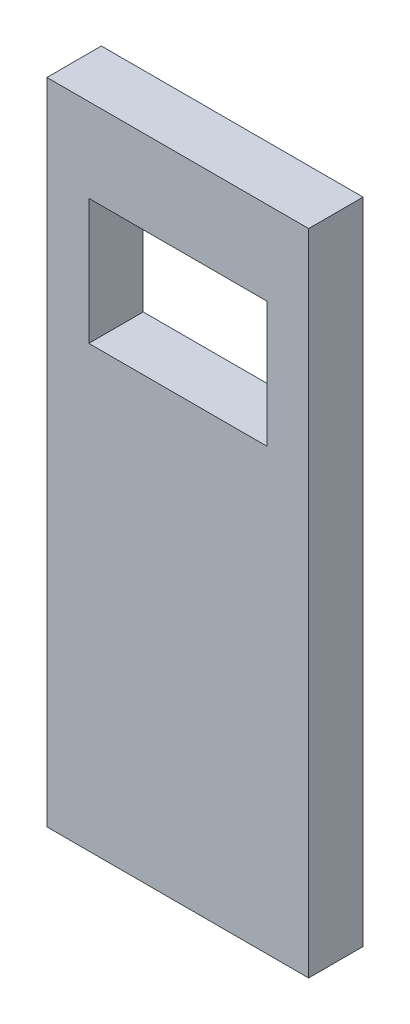
SolidWorks part; units mm, degrees
ref_plane "Front Plane" through (0, 0, 0) normal (0, 0, 1) x (1, 0, 0)
ref_plane "Top Plane" through (0, 0, 0) normal (0, 1, 0) x (1, 0, 0)
ref_plane "Right Plane" through (0, 0, 0) normal (1, 0, 0) x (0, 0, -1)
sketch "Sketch1" plane through (0, 0, 0) normal (0, 0, 1) x (1, 0, 0)
  line L0 (0, 62) -> (0, 42)
  line L1 (0, 62) -> (25, 62)
  line L2 (0, 42) -> (0, 37)
  line L3 (25, 0) -> (0, 0)
  line L4 (4, 54) -> (21, 54)
  line L5 (4, 42) -> (21, 42)
  line L6 (4, 54) -> (4, 42)
  line L7 (21, 54) -> (21, 42)
  line L8 (0, 42) -> (25, 42) construction
  line L9 (0, 37) -> (25, 37) construction
  line L10 (0, 37) -> (0, 25)
  line L11 (0, 25) -> (0, 20)
  line L12 (25, 42) -> (25, 37)
  line L13 (25, 62) -> (25, 42)
  line L14 (0, 20) -> (0, 0)
  line L15 (25, 37) -> (25, 25)
  line L16 (25, 25) -> (25, 20)
  line L17 (25, 20) -> (25, 0)
  line L18 (0, 25) -> (25, 25) construction
  line L19 (25, 20) -> (0, 20) construction
  line L20 (12.5, -0.0005) -> (12.5, 4.0956) construction
  point P18 (12.5, 42)
  point P20 (12.5, 54)
  point P21 (12.5, 62)
  dimension "D1" = 20
  dimension "D2" = 12
  dimension "D3" = 5
  dimension "D4" = 25
  dimension "D5" = 12
  dimension "D6" = 17
extrude "Boss-Extrude1" add sketch "Sketch1" along normal mid plane 5.2
